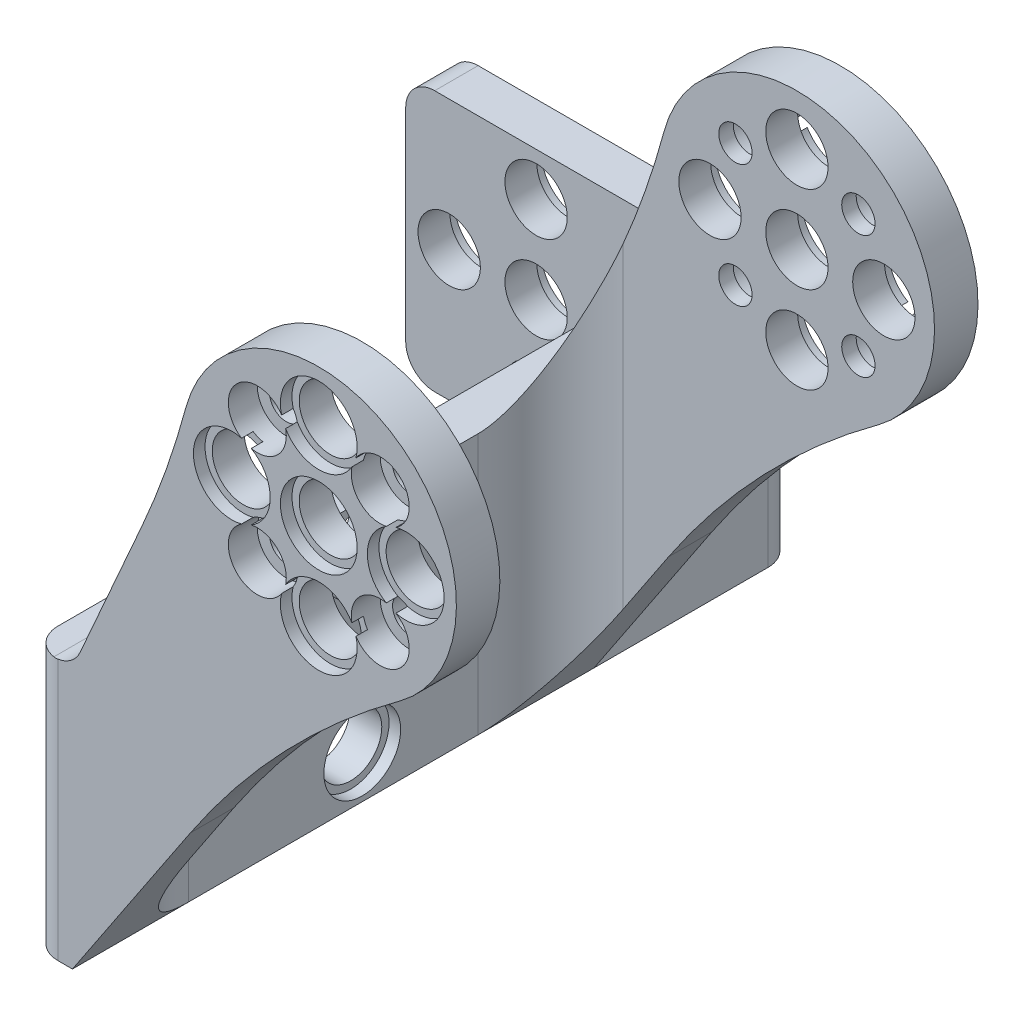
SolidWorks part; units mm, degrees
material "ABS"
ref_plane "Front Plane" through (0, 0, 0) normal (0, 0, 1) x (1, 0, 0)
ref_plane "Top Plane" through (0, 0, 0) normal (0, 1, 0) x (1, 0, 0)
ref_plane "Right Plane" through (0, 0, 0) normal (1, 0, 0) x (0, 0, -1)
sketch "Sketch1" plane through (0, 0, 0) normal (0, 0, 1) x (1, 0, 0)
  line L0 (0, -9.5) -> (-17, -35)
  line L1 (-17, -35) -> (-20, -35)
  line L2 (-20, -35) -> (-20, -17)
  line L3 (-9.5, 0) -> (-17, -17)
  line L5 (-17, -17) -> (-20, -17)
  circle A0 centre (0, 0) radius 9.5 construction
  circle A1 centre (-6, 0) radius 2 construction
  circle A2 centre (0, -6) radius 2 construction
  circle A3 centre (6, 0) radius 2 construction
  circle A4 centre (0, 6) radius 2 construction
  circle A5 centre (-6, 0) radius 2
  circle A6 centre (0, -6) radius 2
  circle A7 centre (6, 0) radius 2
  circle A8 centre (0, 6) radius 2
  arc A9 (0, -9.5) -> (-9.5, 0) centre (0, 0) ccw
  dimension "D1" = 3
extrude "Boss-Extrude1" add sketch "Sketch1" along normal blind 3
sketch "Sketch23" plane through (0, 0, 3) normal (0, 0, 1) x (1, 0, 0)
  circle A0 centre (6, 0) radius 2.15
  circle A1 centre (0, -6) radius 2.15
  circle A2 centre (-6, 0) radius 2.15
  circle A3 centre (0, 6) radius 2.15
  dimension "D1" = 4.3
extrude "Cut-Extrude5" cut sketch "Sketch23" against normal through all
sketch "Sketch2" plane through (0, 0, 0) normal (0, 0, -1) x (-1, 0, 0)
  line L0 (17, -17) -> (20, -17) construction
  line L1 (20, -35) -> (17, -35)
  line L2 (20, -35) -> (20, -17)
  line L3 (20, -17) -> (17, -17)
  line L4 (17, -35) -> (17, -17)
  dimension "D1" = 3
extrude "Boss-Extrude2" add sketch "Sketch2" along normal up to surface (44 mm away)
sketch "Sketch3" plane through (0, 0, -30) normal (0, 0, -1) x (-1, 0, 0)
  line L0 (20, -17) -> (17, -17)
  line L1 (17, -17) -> (9.5, 0)
  line L2 (20, -17) -> (20, -35)
  line L3 (20, -35) -> (17, -35)
  line L4 (17, -35) -> (0, -9.5)
  circle A0 centre (0, 0) radius 9.5 construction
  arc A1 (9.5, 0) -> (0, -9.5) centre (0, 0) ccw
  circle A2 centre (-6, 0) radius 2.15 construction
  circle A3 centre (0, 6) radius 2.15 construction
  circle A5 centre (6, 0) radius 2.15 construction
  circle A6 centre (0, -6) radius 2.15
  circle A7 centre (-6, 0) radius 2.15
  circle A8 centre (6, 0) radius 2.15
  circle A9 centre (0, 6) radius 2.15
  circle A10 centre (0, -6) radius 2.15 construction
extrude "Boss-Extrude3" add sketch "Sketch3" along normal blind 3
sketch "Sketch5" plane through (0, 0, 3) normal (0, 0, 1) x (1, 0, 0)
  circle A0 centre (0, -6) radius 2.65
  circle A1 centre (-6, 0) radius 2.65
  circle A2 centre (0, 6) radius 2.65
  circle A3 centre (6, 0) radius 2.65
  circle A4 centre (0, -6) radius 2.15 construction
  dimension "D1" = 5.3
extrude "Cut-Extrude1" cut sketch "Sketch5" against normal blind 0.8
sketch "Sketch11" plane through (0, 0, -33) normal (0, 0, -1) x (-1, 0, 0)
  circle A0 centre (0, 6) radius 2.65
  circle A1 centre (-6, 0) radius 2.65
  circle A2 centre (0, -6) radius 2.65
  circle A3 centre (6, 0) radius 2.65
  dimension "D1" = 5.3
extrude "Cut-Extrude2" cut sketch "Sketch11" against normal blind 0.8
sketch "Sketch12" plane through (0, 0, -44) normal (0, 0, -1) x (-1, 0, 0)
  line L1 (41, -35) -> (17, -35)
  line L2 (41, -35) -> (41, -17)
  line L3 (41, -17) -> (17, -17)
  line L4 (17, -35) -> (17, -17)
  circle A0 centre (38, -26) radius 2 construction
  circle A1 centre (32, -32) radius 2 construction
  circle A2 centre (32, -26) radius 2 construction
  circle A3 centre (32, -20) radius 2 construction
  circle A4 centre (26, -26) radius 2 construction
  circle A5 centre (38, -26) radius 2
  circle A6 centre (32, -32) radius 2
  circle A7 centre (32, -26) radius 2
  circle A8 centre (32, -20) radius 2
  circle A9 centre (26, -26) radius 2
extrude "Boss-Extrude4" add sketch "Sketch12" along normal blind 3
sketch "Sketch24" plane through (0, 0, -47) normal (0, 0, -1) x (-1, 0, 0)
  circle A0 centre (32, -20) radius 2.15
  circle A1 centre (26, -26) radius 2.15
  circle A2 centre (32, -26) radius 2.15
  circle A3 centre (38, -26) radius 2.15
  circle A4 centre (32, -32) radius 2.15
  dimension "D1" = 4.3
extrude "Cut-Extrude6" cut sketch "Sketch24" against normal through all
sketch "Sketch13" plane through (-20, 0, 0) normal (-1, 0, 0) x (0, 0, 1)
  point P0 (-17, -32)
  point P1 (-17, -20)
hole_wizard "Hole1" positions "Sketch15" profile "Sketch14" legacy
sketch "Sketch15" plane through (-17, 0, 0) normal (1, 0, 0) x (0, 0, -1)
  point P0 (17, -20)
  point P3 (17, -32)
sketch "Sketch14" plane through (-17, -20, -17) normal (0, 1, 0) x (0, 0, -1)
  line L0 (0, 0) -> (0, 3)
  line L1 (0, 3) -> (2.15, 3)
  line L2 (2.15, 3) -> (2.15, 0.8)
  line L3 (2.15, 0.8) -> (2.65, 0.8)
  line L4 (2.65, 0.8) -> (2.65, 0)
  line L5 (2.65, 0) -> (0, 0)
  line L6 (0, 110) -> (0, -10) construction
  dimension "Diameter" = 4.3
  dimension "Depth" = 3
  dimension "C-Bore Diameter" = 5.3
  dimension "C-Bore Depth" = 0.8
sketch "Sketch6" plane through (0, 0, 3) normal (0, 0, 1) x (1, 0, 0)
  point P0 (-4.2426, -4.2426)
  point P1 (-4.2426, 4.2426)
  point P3 (4.2426, 4.2426)
  point P5 (4.2426, -4.2426)
sketch "Sketch22" plane through (0, 0, -47) normal (0, 0, -1) x (-1, 0, 0)
  circle A0 centre (32, -32) radius 2.65
  circle A1 centre (38, -26) radius 2.65
  circle A2 centre (32, -26) radius 2.65
  circle A3 centre (32, -20) radius 2.65
  circle A4 centre (26, -26) radius 2.65
  circle A5 centre (32, -26) radius 2.15 construction
  circle A6 centre (26, -26) radius 2.15 construction
  circle A7 centre (32, -20) radius 2.15 construction
  circle A8 centre (38, -26) radius 2.15 construction
  circle A9 centre (32, -32) radius 2.15 construction
  dimension "D1" = 5.3
extrude "Cut-Extrude4" cut sketch "Sketch22" against normal blind 0.8
hole_wizard "CBORE for M1.6 Hex Socket Head Cap Screw1" positions "Sketch8" profile "Sketch7" counterbore size "M1.6" standard "ISO"
sketch "Sketch8" plane through (0, 0, 3) normal (0, 0, 1) x (1, 0, 0)
  point P0 (-4.2426, -4.2426)
  point P3 (4.2426, -4.2426)
  point P6 (4.2426, 4.2426)
  point P9 (-4.2426, 4.2426)
sketch "Sketch7" plane through (-4.2426, -4.2426, 3) normal (1, 0, 0) x (0, -1, 0)
  line L0 (0, 0) -> (0, 3)
  line L1 (0, 3) -> (1.15, 3)
  line L3 (1.15, 3) -> (1.15, 2)
  line L4 (1.15, 2) -> (2, 2)
  line L5 (2, 2) -> (2, 0)
  line L7 (2, 0) -> (0, 0)
  line L11 (0, -6.35) -> (0, 107.95) construction
  dimension "Thru Hole Dia." = 2.3
  dimension "Thru Hole Depth" = 3
  dimension "C'Bore Dia." = 4
  dimension "C'Bore Depth" = 2
hole_wizard "CBORE for M1.6 Hex Socket Head Cap Screw2" positions "Sketch10" profile "Sketch9" counterbore size "M1.6" standard "ISO" end condition up to next
sketch "Sketch10" plane through (0, 0, -33) normal (0, 0, -1) x (-1, 0, 0)
  point P0 (4.2426, 4.2426)
  point P3 (4.2426, -4.2426)
  point P6 (-4.2426, -4.2426)
  point P9 (-4.2426, 4.2426)
sketch "Sketch9" plane through (-4.2426, 4.2426, -33) normal (1, 0, 0) x (0, 1, 0)
  line L0 (0, 0) -> (0, 3)
  line L1 (0, 3) -> (1.15, 3)
  line L3 (1.15, 3) -> (1.15, 2)
  line L4 (1.15, 2) -> (2, 2)
  line L5 (2, 2) -> (2, 0)
  line L7 (2, 0) -> (0, 0)
  line L11 (0, -6.35) -> (0, 107.95) construction
  dimension "Thru Hole Dia." = 2.3
  dimension "Thru Hole Depth" = 3
  dimension "C'Bore Dia." = 4
  dimension "C'Bore Depth" = 2
sketch "Sketch17" plane through (0, 0, 3) normal (0, 0, 1) x (1, 0, 0)
  point P0 (0, 0)
hole_wizard "Hole2" positions "Sketch19" profile "Sketch18" legacy
sketch "Sketch19" plane through (0, 0, 3) normal (0, 0, 1) x (1, 0, 0)
  point P0 (0, 0)
sketch "Sketch18" plane through (0, 0, 3) normal (1, 0, 0) x (0, -1, 0)
  line L0 (0, 0) -> (0, 3)
  line L1 (0, 3) -> (2.15, 3)
  line L2 (2.15, 3) -> (2.15, 0.8)
  line L3 (2.15, 0.8) -> (2.65, 0.8)
  line L4 (2.65, 0.8) -> (2.65, 0)
  line L5 (2.65, 0) -> (0, 0)
  line L6 (0, 110) -> (0, -10) construction
  dimension "Diameter" = 4.3
  dimension "Depth" = 3
  dimension "C-Bore Diameter" = 5.3
  dimension "C-Bore Depth" = 0.8
hole_wizard "Hole3" positions "Sketch21" profile "Sketch20" legacy
sketch "Sketch21" plane through (0, 0, -33) normal (0, 0, -1) x (-1, 0, 0)
  point P0 (0, 0)
sketch "Sketch20" plane through (0, 0, -33) normal (1, 0, 0) x (0, 1, 0)
  line L0 (0, 0) -> (0, 3)
  line L1 (0, 3) -> (2.15, 3)
  line L2 (2.15, 3) -> (2.15, 0.8)
  line L3 (2.15, 0.8) -> (2.65, 0.8)
  line L4 (2.65, 0.8) -> (2.65, 0)
  line L5 (2.65, 0) -> (0, 0)
  line L6 (0, 110) -> (0, -10) construction
  dimension "Diameter" = 4.3
  dimension "Depth" = 3
  dimension "C-Bore Diameter" = 5.3
  dimension "C-Bore Depth" = 0.8
fillet "Fillet10" radius 2 1 edges at (-17, -17, 1.5)
fillet "Fillet5" radius 2 4 edges at (-41, -17, -45.5) (-41, -35, -45.5) (-17, -26, -47) (-20, -26, 3)
chamfer "Chamfer2" distance 2 angle 45 1 edges
fillet "Fillet7" radius 60 4 edges at (-9.5, 0, 1.5) (-9.5, 0, -31.5) (0, -9.5, 1.5) (0, -9.5, -31.5)
fillet "Redondeo1" radius 5 2 edges at (-17, -26, -30) (-17, -26, 0)
